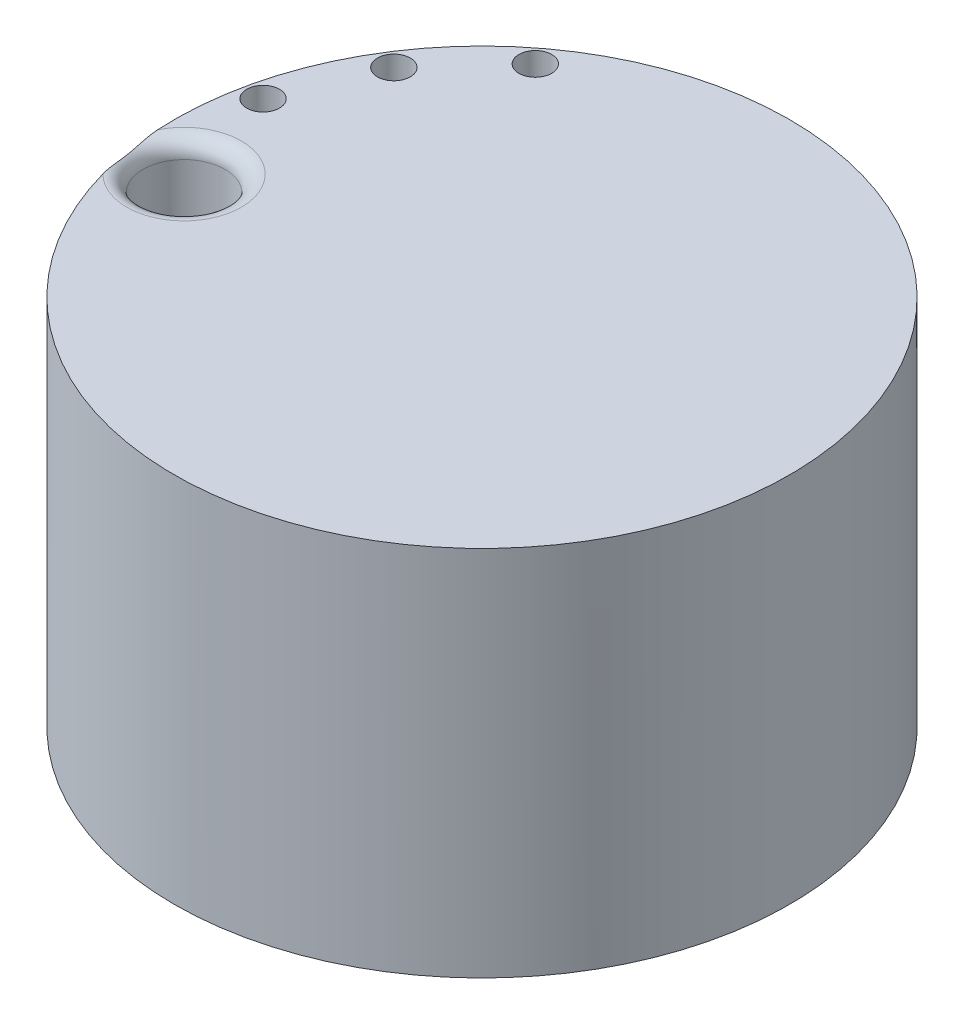
SolidWorks part; units mm, degrees
ref_plane "Front Plane" through (0, 0, 0) normal (0, 0, 1) x (1, 0, 0)
ref_plane "Top Plane" through (0, 0, 0) normal (0, 1, 0) x (1, 0, 0)
ref_plane "Right Plane" through (0, 0, 0) normal (1, 0, 0) x (0, 0, -1)
sketch "Sketch2" plane through (0, 0, 0) normal (0, 1, 0) x (1, 0, 0)
  circle A0 centre (0, 0) radius 47.6885
  dimension "D1" = 95.377
extrude "Boss-Extrude1" add sketch "Sketch2" along normal blind 57.658
sketch "Sketch4" plane through (0, 57.658, 0) normal (0, 1, 0) x (1, 0, 0)
  circle A1 centre (-26.162, 0) radius 3.175
  circle A2 centre (26.162, 0) radius 3.175
  circle A3 centre (0, 26.162) radius 3.175
  circle A4 centre (0, -26.162) radius 3.175
sketch "Sketch5" plane through (0, 57.658, 0) normal (0, 1, 0) x (1, 0, 0)
  line L0 (0, 0) -> (-37.6709, 24.0132)
  line L1 (0, 0) -> (-27.1861, 35.4492)
  line L2 (0, 0) -> (-43.6121, 9.6808)
  line L3 (-45.9654, -6.5579) -> (-47.2354, -6.5579)
  line L4 (0, 0) -> (-39.6154, -6.5579)
  circle A1 centre (-27.1861, 35.4492) radius 2.54
  circle A2 centre (0, 0) radius 44.6736
  circle A3 centre (-37.6709, 24.0132) radius 2.54
  circle A4 centre (-43.6121, 9.6808) radius 2.54
  circle A9 centre (-39.6154, -6.5579) radius 6.35
  circle A10 centre (0, 0) radius 47.6885 construction
  dimension "D1" = 20
  dimension "D2" = 20
  dimension "D3" = 12.7
  dimension "D5" = 89.3472
  dimension "D4" = 1.27
extrude "Cut-Extrude2" cut sketch "Sketch5" against normal through all contours A9 | A1 | A3 | A4
fillet "Fillet1" radius 2.54 1 edges at (-39.6154, 57.658, 12.9079)
sketch "Sketch6" plane through (0, 0, 0) normal (0, -1, 0) x (1, 0, 0)
  line L0 (0, 0) -> (-37.6709, -24.0132)
  line L1 (0, 0) -> (25.6337, -40.2132)
  line L3 (19.4654, -39.2136) -> (27.3315, -34.1994)
  line L4 (19.4654, -39.2136) -> (17.5588, -36.2227)
  line L5 (27.3315, -34.1994) -> (25.4249, -31.2085)
  line L6 (17.5588, -36.2227) -> (25.4249, -31.2085)
  line L7 (19.4654, -39.2136) -> (25.4249, -31.2085) construction
  line L8 (27.3315, -34.1994) -> (17.5588, -36.2227) construction
  circle A0 centre (0, 0) radius 47.6885 construction
  point P4 (0, 0)
  point P8 (-33.1066, -26.1952)
  point P9 (-27.9455, -29.5928)
  point P10 (22.4451, -35.2111)
  point P11 (0, 0)
  point P12 (22.4451, -35.2111)
  point P13 (0, 0)
  point P18 (0, 0)
  point P19 (-36.2052, -26.9976)
  point P20 (-28.3709, -30.0433)
  point P21 (-31.4686, -24.4972)
  point P22 (-33.2779, -28.4463)
